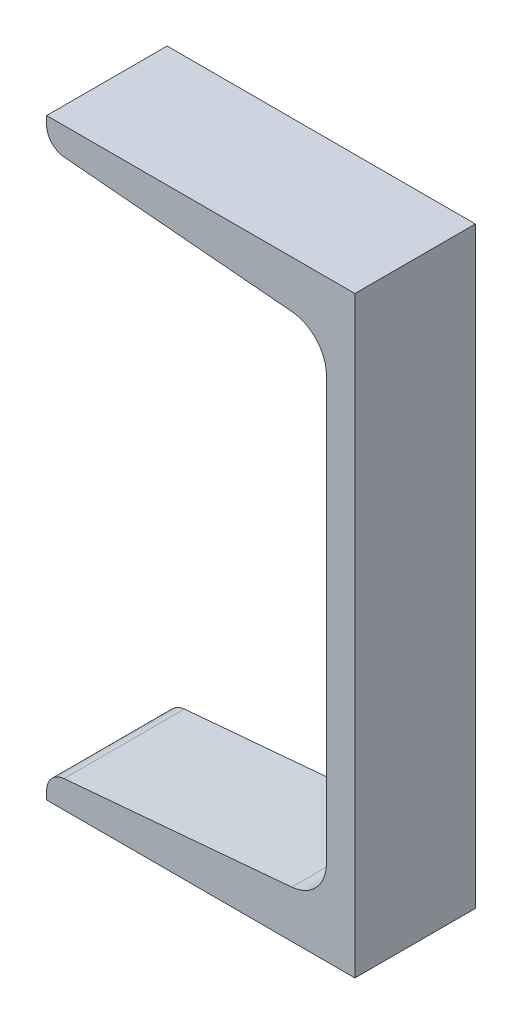
SolidWorks part; units mm, degrees
ref_plane "Front Plane" through (0, 0, 0) normal (0, 0, 1) x (1, 0, 0)
ref_plane "Top Plane" through (0, 0, 0) normal (0, 1, 0) x (1, 0, 0)
ref_plane "Right Plane" through (0, 0, 0) normal (1, 0, 0) x (0, 0, -1)
sketch "Sketch1" plane through (0, 0, 0) normal (0, 0, 1) x (1, 0, 0)
  line L0 (0, 84.7619) -> (0, -74.8933) construction
  line L1 (-65, 62.5) -> (0, 62.5)
  line L2 (-65, 62.5) -> (-65, 60.7462)
  line L3 (-65, -62.5) -> (0, -62.5)
  line L4 (0, 62.5) -> (0, -62.5)
  line L5 (-42.3074, 0) -> (60.8749, 0) construction
  line L6 (-65, -60.7462) -> (-65, -62.5)
  line L7 (-61.3486, 56.7615) -> (-13.3028, 52.558)
  line L9 (-61.3486, -56.7615) -> (-13.3028, -52.558)
  line L10 (-6, 44.5884) -> (-6, -44.5884)
  line L14 (-65, 21.4066) -> (-6, 21.4066) construction
  line L15 (-35.5, 62.5) -> (-35.5, 54.5) construction
  line L16 (-35.5, 54.5) -> (-35.5, 21.4066) construction
  arc A0 (-13.3028, 52.558) -> (-6, 44.5884) centre (-14, 44.5884) cw
  arc A1 (-13.3028, -52.558) -> (-6, -44.5884) centre (-14, -44.5884) ccw
  arc A4 (-65, 60.7462) -> (-61.3486, 56.7615) centre (-61, 60.7462) ccw
  arc A5 (-65, -60.7462) -> (-61.3486, -56.7615) centre (-61, -60.7462) cw
  point P18 (0, -62.5)
  point P27 (0, 62.5)
  point P34 (-65, 57.0809)
  point P37 (-65, -57.0809)
  dimension "Radius_root" = 8
  dimension "Radius_toe" = 4
  dimension "Depth" = 125
  dimension "Width" = 65
  dimension "Web_thickness" = 6
  dimension "Thickness" = 8
  dimension "D1" = 95
extrude "BaseSection" add sketch "Sketch1" along normal mid plane 25.4
